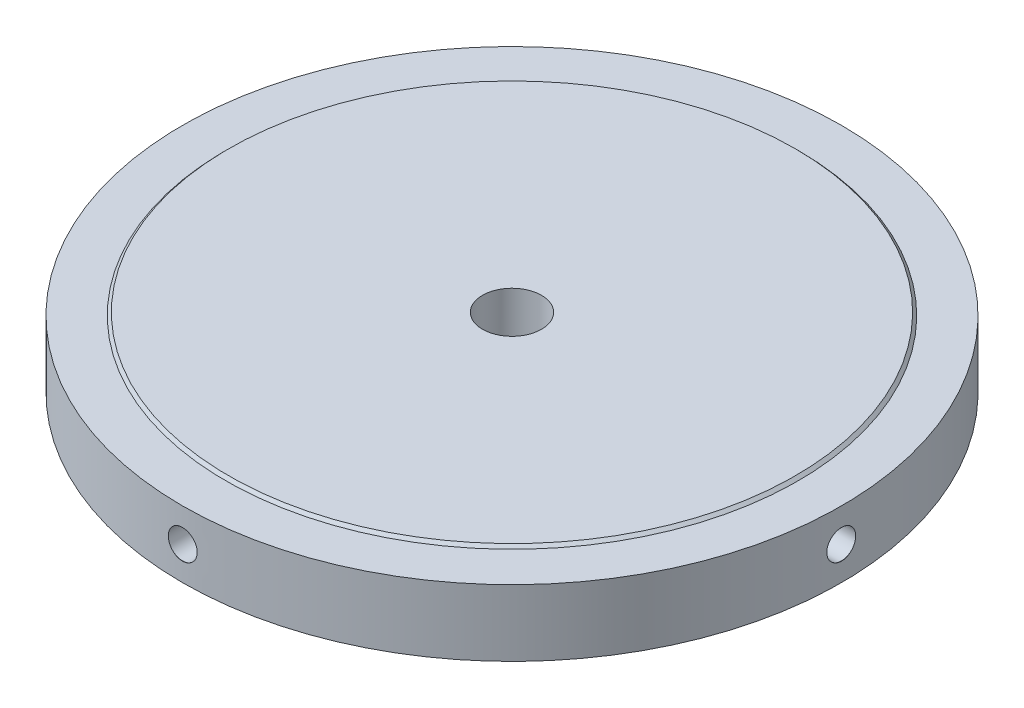
SolidWorks part; units mm, degrees
material "Polyetheretherketone (PEEK)"
ref_plane "Front Plane" through (0, 0, 0) normal (0, 0, 1) x (1, 0, 0)
ref_plane "Top Plane" through (0, 0, 0) normal (0, 1, 0) x (1, 0, 0)
ref_plane "Right Plane" through (0, 0, 0) normal (1, 0, 0) x (0, 0, -1)
sketch "Sketch1" plane through (0, 0, 0) normal (0, 0, 1) x (1, 0, 0)
  line L0 (0, 0) -> (0, 50000) construction
  line L1 (0, 6.25) -> (49, 6.25)
  line L3 (0, 6.25) -> (0, -5.75)
  line L4 (0, -5.75) -> (57, -5.75)
  line L5 (57, 5.75) -> (57, -5.75)
  line L7 (57, 5.75) -> (49.5, 5.75)
  line L10 (49, 6.25) -> (49.5, 5.75)
  point P7 (57, 0)
  dimension "D1" = 11.5
  dimension "D2" = 114
  dimension "D3" = 98
  dimension "D4" = 0.5
  dimension "D5" = 0.5
revolve "Revolve1" add sketch "Sketch1" angle 360 about L0
hole_wizard "M5 Tapped Hole1" positions "3DSketch1" profile "Sketch2" tap size "M5" standard "ISO"
sketch3d "3DSketch1"
  circle A0 centre (0, 0, 0) radius 57 construction
  point P0 (57, 0, 0)
  point P2 (0, 0, 57)
  point P4 (-57, 0, 0)
  point P6 (0, 0, -57)
  point P11 (0, 57, 0)
sketch "Sketch2" plane through (57, 0, 0) normal (0, 1, 0) x (0, 0, -1)
  line L0 (0, 0) -> (0, 15.2618)
  line L1 (0, 15.2618) -> (2.1, 14)
  line L2 (2.1, 14) -> (2.1, 10)
  line L3 (2.1, 10) -> (2.5, 10)
  line L5 (2.5, 10) -> (2.5, 0.025)
  line L6 (2.5, 0.025) -> (2.525, 0)
  line L7 (2.525, 0) -> (0, 0)
  line L8 (-2.5, 0.025) -> (-2.525, 0) construction
  line L10 (0, 15.2618) -> (-2.1, 14) construction
  line L11 (0, -6.35) -> (0, 107.95) construction
  dimension "Tap Drill Dia." = 4.2
  dimension "Tap Drill Depth" = 14
  dimension "Thread Major Dia." = 5
  dimension "Thread Depth" = 10
  dimension "Near C'Sink Dia." = 5.05
  dimension "Near C'Sink Angle" = 90
  dimension "Drill Angle" = 118
hole_wizard "M12 Tapped Hole1" positions "Sketch3" profile "Sketch4" tap size "M12" standard "ISO" end condition up to next
sketch "Sketch3" plane through (0, 6.25, 0) normal (0, 1, 0) x (1, 0, 0)
  point P2 (0, 0)
sketch "Sketch4" plane through (0, 6.25, 0) normal (1, 0, 0) x (0, 0, 1)
  line L0 (0, 0) -> (0, 12)
  line L1 (0, 12) -> (5.1, 12)
  line L2 (5.1, 12) -> (5.1, 0)
  line L5 (5.1, 0) -> (0, 0)
  line L11 (0, -6.35) -> (0, 107.95) construction
  dimension "Thru Tap Drill Dia." = 10.2
  dimension "Thru Tap Drill Depth" = 12
cosmetic thread "Hole Thread10" parameters "D2"=12
equation "\"CanSat_Len\"= 400mm"
equation "\"CanSat_Dia\"= 150mm"
equation "\"BodyTube_ID\"= 114mm"
equation "\"BodyTube_OD\"= 120mm"
equation "\"PayLoadBay_ID\"= 164mm"
equation "\"PayLoadBay_OD\"= 170mm"
equation "\"ParachuteBay_Pitch\"= 300mm"
equation "\"ElectronicsTray_PitchDist\"= 50mm"
equation "\"ElectronicsTray_Height\"= 140mm"
equation "\"D2@Sketch1\"=\"BodyTube_ID\""
